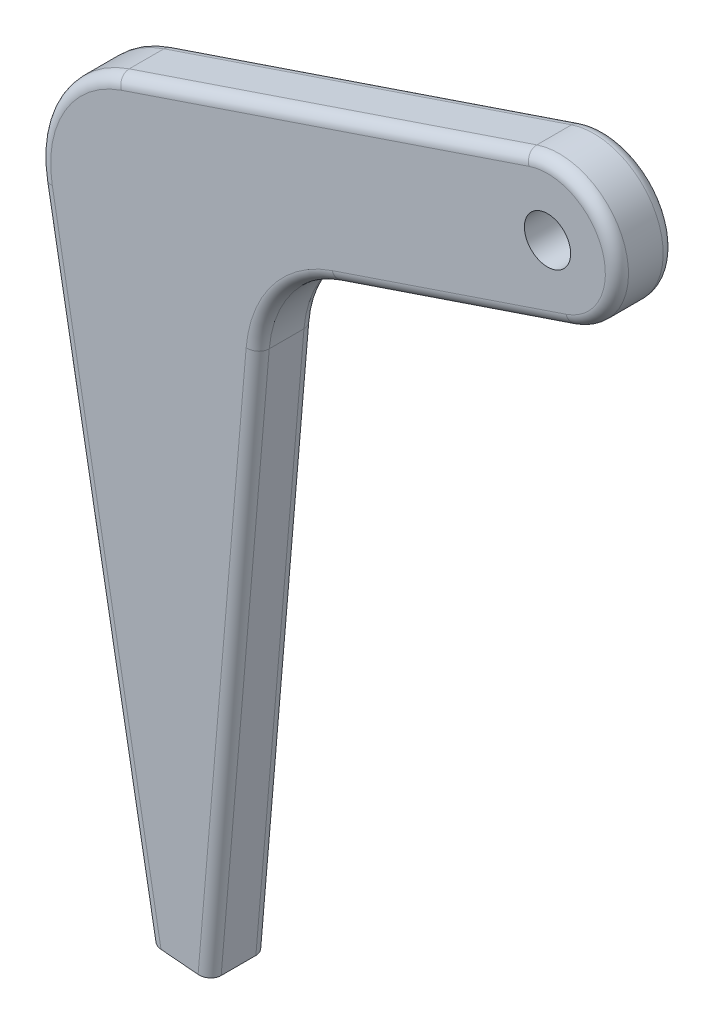
SolidWorks part; units mm, degrees
ref_plane "Front Plane" through (0, 0, 0) normal (0, 0, 1) x (1, 0, 0)
ref_plane "Top Plane" through (0, 0, 0) normal (0, 1, 0) x (1, 0, 0)
ref_plane "Right Plane" through (0, 0, 0) normal (1, 0, 0) x (0, 0, -1)
sketch "Sketch1" plane through (0, 0, 0) normal (0, 0, 1) x (1, 0, 0)
  line L0 (-10, -50) -> (-26.1505, -130.7992) construction
  line L2 (-8.0767, -55.6834) -> (-28.3007, -62.5274)
  line L3 (-47.1637, -56.2424) -> (-11.9233, -44.3166)
  line L4 (-44.4467, -119.7167) -> (-53.8015, -67.4774)
  line L5 (-39.2152, -120.1603) -> (-44.4467, -119.7167)
  line L6 (-35.0594, -71.1547) -> (-39.2152, -120.1603)
  circle A1 centre (-10, -50) radius 2
  arc A2 (-35.0594, -71.1547) -> (-28.3007, -62.5274) centre (-25.0952, -71.9997) cw
  arc A9 (-11.9233, -44.3166) -> (-8.0767, -55.6834) centre (-10, -50) cw
  arc A10 (-53.8015, -67.4774) -> (-47.1637, -56.2424) centre (-43.9581, -65.7147) cw
extrude "Boss-Extrude1" add sketch "Sketch1" along normal mid plane 5
fillet "Fillet1" radius 1 14 edges at (-37.1373, -95.6575, -2.5) (-32.9672, -65.8328, -2.5) (-49.1241, -93.597, -2.5) (-52.5677, -60.6279, -2.5) (-29.5435, -50.2795, -2.5) (-4.3166, -48.0767, -2.5) (-37.1373, -95.6575, 2.5) (-32.9672, -65.8328, 2.5) (-49.1241, -93.597, 2.5) (-52.5677, -60.6279, 2.5) (-29.5435, -50.2795, 2.5) (-4.3166, -48.0767, 2.5) (-18.1887, -59.1054, -2.5) (-18.1887, -59.1054, 2.5)
